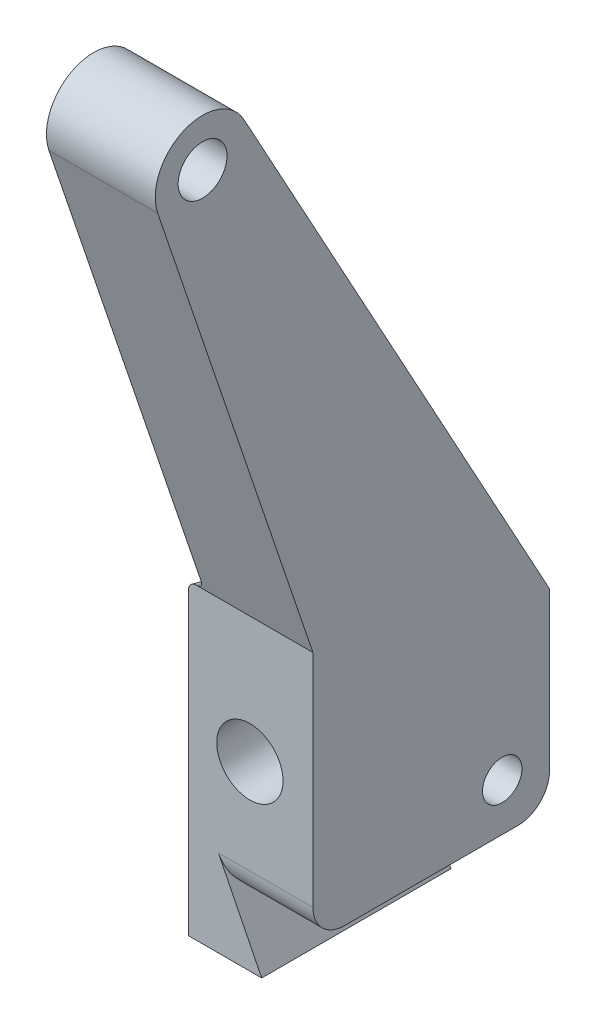
SolidWorks part; units mm, degrees
ref_plane "Front Plane" through (0, 0, 0) normal (0, 0, 1) x (1, 0, 0)
ref_plane "Top Plane" through (0, 0, 0) normal (0, 1, 0) x (1, 0, 0)
ref_plane "Right Plane" through (0, 0, 0) normal (1, 0, 0) x (0, 0, -1)
sketch "Sketch1" plane through (0, 0, 0) normal (1, 0, 0) x (0, 0, -1)
  line L0 (0, 0) -> (0, 16)
  line L1 (0, 16) -> (-19.3675, 51.4387)
  line L2 (-15, 20) -> (-15, 0)
  line L3 (-15, 0) -> (0, 0)
  line L4 (-15, 20) -> (-24.8413, 49.037)
  arc A0 (-19.3675, 51.4387) -> (-24.8413, 49.037) centre (-22, 50) ccw
  circle A1 centre (-22, 50) radius 1.55
  dimension "D4" = 6
  dimension "D5" = 22
  dimension "D6" = 50
  dimension "D7" = 3.1
  dimension "D1" = 20
  dimension "D2" = 16
  dimension "D3" = 15
extrude "Boss-Extrude1" add sketch "Sketch1" along normal blind 7.9
sketch "Sketch2" plane through (7.9, 0, 0) normal (1, 0, 0) x (0, 0, -1)
  line L0 (-15, 20) -> (-15, 0) construction
  line L1 (-15, 5) -> (0, 5)
  line L2 (-15, 5) -> (-15, 0)
  line L3 (-15, 0) -> (0, 0)
  line L4 (0, 5) -> (0, 0)
  line L5 (0, 0) -> (0, 16) construction
  dimension "D1" = 5
extrude "Cut-Extrude1" [suppressed] cut sketch "Sketch2" against normal blind 4
sketch "Sketch3" plane through (0, 0, 0) normal (0, 0, -1) x (-1, 0, 0)
  line L0 (-7.9, 0) -> (-4.9, 0)
  line L1 (-7.9, 0) -> (0, 0) construction
  line L2 (-4.9, 0) -> (-2.9, 4)
  line L3 (-2.9, 4) -> (-7.9, 4)
  line L4 (-7.9, 0) -> (-7.9, 16) construction
  line L5 (-7.9, 4) -> (-7.9, 0)
  dimension "D1" = 5
  dimension "D2" = 3
  dimension "D3" = 4
extrude "Cut-Extrude2" cut sketch "Sketch3" against normal through all
sketch "Sketch5" plane through (7.9, 0, 0) normal (1, 0, 0) x (0, 0, -1)
  line L0 (0, 4) -> (0, 16) construction
  line L1 (-15, 4) -> (0, 4) construction
  circle A0 centre (-3, 7) radius 1
  dimension "D1" = 2
  dimension "D3" = 3
  dimension "D2" = 3
hole_wizard "M3x0.5 Tapped Hole1" positions "3DSketch1" profile "Sketch6" tap size "M3x0.5" standard "ANSI Metric" end condition through all
sketch3d "3DSketch1"
  point P0 (7.9, 7, 3)
sketch "Sketch6" plane through (7.9, 7, 3) normal (0, 1, 0) x (0, 0, -1)
  line L0 (0, 0) -> (0, 7.9)
  line L1 (0, 7.9) -> (1.25, 7.9)
  line L2 (1.25, 7.9) -> (1.25, 0)
  line L5 (1.25, 0) -> (0, 0)
  line L11 (0, -6.35) -> (0, 107.95) construction
  dimension "Thread Major Dia." = 2.5
  dimension "Thru Tap Drill Depth" = 7.9
sketch "Sketch7" plane through (0, 0, 0) normal (0, 0, -1) x (-1, 0, 0)
  line L1 (0, 0) -> (-8, 0)
  line L2 (0, 0) -> (0, 0.5)
  line L3 (0, 0.5) -> (-8, 0.5)
  line L4 (-8, 0) -> (-8, 0.5)
  dimension "D1" = 0.5
  dimension "D2" = 8
extrude "Cut-Extrude3" cut sketch "Sketch7" against normal through all
sketch "Sketch8" plane through (0, 0, 15) normal (0, 0, 1) x (1, 0, 0)
  line L0 (2.9, 4) -> (7.9, 4) construction
  line L1 (7.9, 20) -> (7.9, 4) construction
  circle A0 centre (3.9, 12) radius 2.1
  point P4 (5.4, 4)
  dimension "D1" = 4.2
  dimension "D2" = 8
  dimension "D3" = 4
extrude "Cut-Extrude4" cut sketch "Sketch8" against normal through all
sketch "Sketch9" plane through (0, 0, 0) normal (0, 0, -1) x (-1, 0, 0)
  line L0 (-4.65, 0.5) -> (-2.9, 4)
  line L1 (-2.9, 4) -> (0, 4)
  line L2 (0, 0.5) -> (0, 16) construction
  line L3 (0, 4) -> (0, 0.5)
  line L4 (0, 0.5) -> (-4.65, 0.5)
extrude "Cut-Extrude5" cut sketch "Sketch9" against normal blind 3
sketch "Sketch11" plane through (0, 0, 0) normal (-1, 0, 0) x (0, 0, 1)
  line L0 (0, 16) -> (15, 20)
  line L1 (15, 20) -> (24.8413, 49.037)
  line L2 (19.3675, 51.4387) -> (0, 16)
  arc A0 (24.8413, 49.037) -> (19.3675, 51.4387) centre (22, 50) ccw
extrude "Cut-Extrude6" cut sketch "Sketch11" against normal blind 1
sketch "Sketch14" plane through (1, 0, 0) normal (-1, 0, 0) x (0, 0, 1)
  line L0 (0, 16) -> (13.9073, 41.4477)
  line L1 (19.3675, 51.4387) -> (0, 16) construction
  line L2 (15, 0.5) -> (3, 0.5) construction
  arc A0 (0, 16) -> (13.9073, 41.4477) centre (1.0183, 31.9676) ccw
  dimension "D2" = 16
  dimension "D1" = 29
  dimension "D3" = 15.5
extrude "Cut-Extrude8" [suppressed] cut sketch "Sketch14" against normal mid plane 7.8
hole_wizard "Tap Drill for M3x0.5 Tap" [suppressed] positions "3DSketch2" profile "Sketch17" hole size "M3x0.5" standard "ANSI Metric"
sketch3d "3DSketch2"
  point P0 (-47.3088, 48.5293, 124.6628)
  point P3 (22.4912, 48.5293, 124.6628)
sketch "Sketch17" plane through (-67.715, 0, 23.1968) normal (1, 0, 0) x (0, 0, -1)
  line L0 (0, 0) -> (0, 3.7511)
  line L1 (0, 3.7511) -> (1.25, 3)
  line L2 (1.25, 3) -> (1.25, 0)
  line L3 (1.25, 0) -> (0, 0)
  line L4 (0, 3.7511) -> (-1.25, 3) construction
  line L5 (0, -6.35) -> (0, 107.95) construction
  dimension "Hole Dia." = 2.5
  dimension "Hole Depth" = 3
  dimension "Drill Angle" = 118
fillet "Fillet1" [suppressed] radius 1
fillet "Fillet2" [suppressed] radius 0.5
fillet "Fillet3" [suppressed] radius 0.5
fillet "Fillet4" radius 0.5 2 edges at (1, 18, 7.5) (0, 18, 7.5)
sketch "Sketch18" plane through (0, 0, 15) normal (0, 0, 1) x (1, 0, 0)
  line L0 (0, 19.4825) -> (0, 0.5) construction
  line L1 (7.9, 4) -> (0, 4)
  line L2 (7.9, 4) -> (7.9, 0.5)
  line L3 (7.9, 0.5) -> (0, 0.5)
  line L4 (0, 4) -> (0, 0.5)
extrude "Cut-Extrude9" [suppressed] cut sketch "Sketch18" against normal blind 2
fillet "Fillet5" radius 2 2 edges at (3.95, 4, 0) (5.4, 4, 15)
